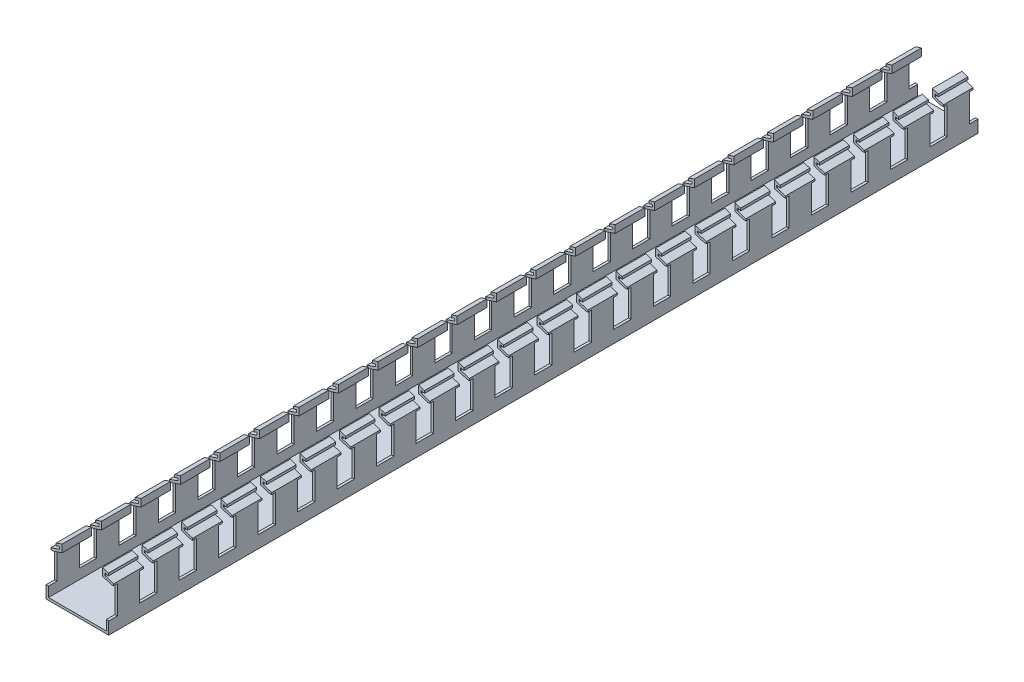
SolidWorks part; units mm, degrees
ref_plane "Alzado" through (0, 0, 0) normal (0, 0, 1) x (1, 0, 0)
ref_plane "Planta" through (0, 0, 0) normal (0, 1, 0) x (1, 0, 0)
ref_plane "Vista lateral" through (0, 0, 0) normal (1, 0, 0) x (0, 0, -1)
sketch "Croquis2" plane through (0, 0, 0) normal (0, 0, 1) x (1, 0, 0)
  line L0 (-12.7, 0) -> (12.7, 0)
  line L1 (0, 0) -> (0, 14.1113) construction
  line L2 (-12.7, 0) -> (-12.7, 17)
  line L4 (8.2, 17.4459) -> (11.7, 16.2792)
  line L5 (8.2, 20.5) -> (8.2, 17.4459)
  line L6 (10.5717, 19.7094) -> (8.2, 20.5)
  line L7 (10.5717, 18.7094) -> (10.5717, 19.7094)
  line L8 (9.2, 18.8892) -> (9.2, 18.3108)
  line L9 (10.5717, 18.7094) -> (9.4632, 19.0789)
  line L10 (-9.3368, 18.1211) -> (-12.7, 17)
  line L11 (-10.5717, 18.7094) -> (-9.4632, 19.0789)
  line L12 (-9.2, 18.8892) -> (-9.2, 18.3108)
  line L13 (9.3368, 18.1211) -> (12.7, 17)
  line L14 (12.7, 0) -> (12.7, 17)
  line L15 (11.7, 16.2792) -> (11.7, 1)
  line L16 (-10.5717, 18.7094) -> (-10.5717, 19.7094)
  line L18 (-10.5717, 19.7094) -> (-8.2, 20.5)
  line L19 (-8.2, 20.5) -> (-8.2, 17.4459)
  line L20 (-8.2, 17.4459) -> (-11.7, 16.2792)
  line L21 (-11.7, 16.2792) -> (-11.7, 1)
  line L22 (-11.7, 1) -> (11.7, 1)
  arc A0 (9.3368, 18.1211) -> (9.2, 18.3108) centre (9.4, 18.3108) cw
  arc A1 (9.2, 18.8892) -> (9.4632, 19.0789) centre (9.4, 18.8892) cw
  arc A4 (-9.2, 18.8892) -> (-9.4632, 19.0789) centre (-9.4, 18.8892) ccw
  arc A5 (-9.3368, 18.1211) -> (-9.2, 18.3108) centre (-9.4, 18.3108) ccw
  dimension "D8" = 0.2
  dimension "D1" = 25.4
  dimension "D2" = 1
  dimension "D3" = 1
  dimension "D4" = 1
  dimension "D5" = 1
  dimension "D6" = 1
  dimension "D7" = 20.5
  dimension "D9" = 8.2
  dimension "D10" = 2.5
  dimension "D11" = 71.565
  dimension "D12" = 3.0541
extrude "Saliente-Extruir1" add sketch "Croquis2" along normal mid plane 16
sketch "Croquis3" plane through (0, 0, 0) normal (1, 0, 0) x (0, 0, -1)
  line L0 (0, 0) -> (0, 24.3686) construction
  line L1 (-8, 0) -> (8, 0) construction
  line L2 (-8, 5) -> (-4.5, 5)
  line L3 (-8, 0) -> (-8, 17) construction
  line L4 (-4.5, 5) -> (-4.5, 16.2792)
  line L5 (-4.5, 16.2792) -> (-6, 16.2792)
  line L6 (-6, 16.2792) -> (-6, 20.5)
  line L7 (-8, 5) -> (-8, 20.5)
  line L8 (-8, 20.5) -> (-6, 20.5)
  line L10 (-8, 20.5) -> (8, 20.5) construction
  line L11 (8, 20.5) -> (6, 20.5)
  line L12 (8, 5) -> (8, 20.5)
  line L13 (6, 16.2792) -> (6, 20.5)
  line L14 (4.5, 16.2792) -> (6, 16.2792)
  line L15 (4.5, 5) -> (4.5, 16.2792)
  line L16 (8, 5) -> (4.5, 5)
  line L17 (-8, 16.2792) -> (8, 16.2792) construction
  dimension "D1" = 5
  dimension "D2" = 3.5
  dimension "D3" = 2
extrude "Cortar-Extruir1" cut sketch "Croquis3" against normal mid plane 66
pattern_linear "MatrizL1" count 22 spacing 16 along (0, 0, -1) of "Saliente-Extruir1", "Cortar-Extruir1"
